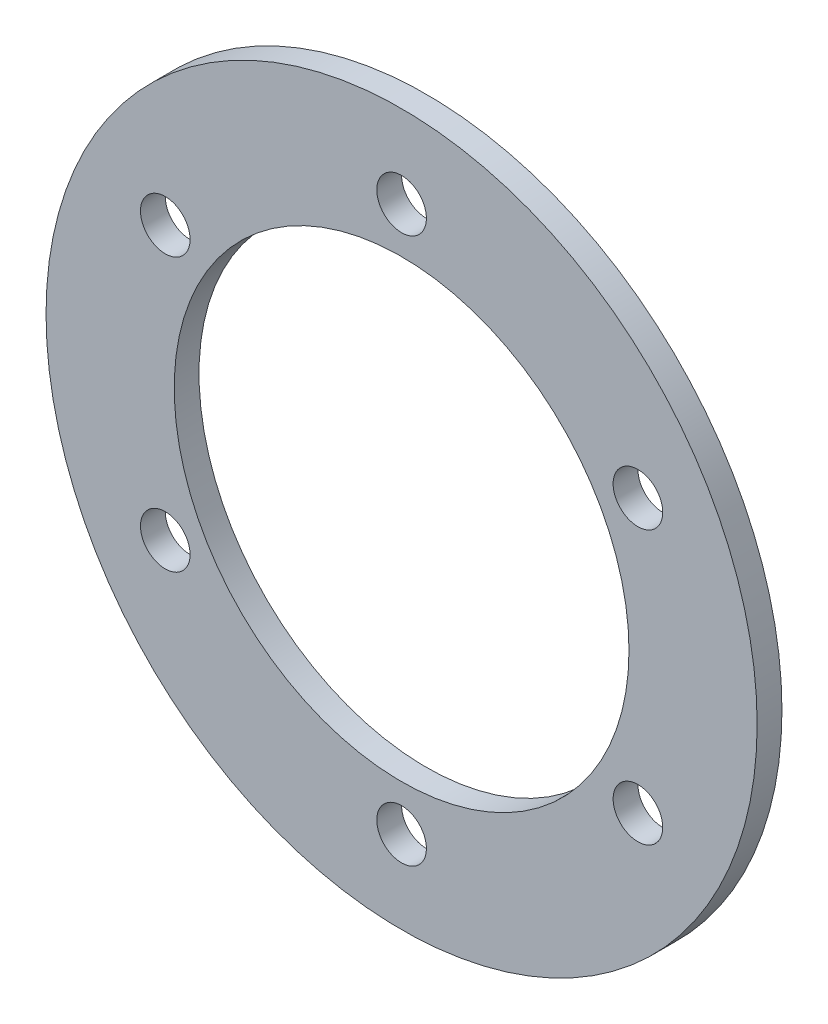
SolidWorks part; units mm, degrees
ref_plane "Front Plane" through (0, 0, 0) normal (0, 0, 1) x (1, 0, 0)
ref_plane "Top Plane" through (0, 0, 0) normal (0, 1, 0) x (1, 0, 0)
ref_plane "Right Plane" through (0, 0, 0) normal (1, 0, 0) x (0, 0, -1)
sketch "Sketch1" plane through (0, 0, 0) normal (0, 0, 1) x (1, 0, 0)
  circle A0 centre (0, 0) radius 43
  circle A1 centre (0, 0) radius 33 construction
  circle A3 centre (0, 33) radius 3
  circle A4 centre (0, 0) radius 27.5
  dimension "D1" = 86
  dimension "D2" = 6
  dimension "D3" = 66
  dimension "D4" = 55
extrude "Boss-Extrude2" add sketch "Sketch1" along normal blind 3 contours A0
extrude "Cut-Extrude1" cut sketch "Sketch1<3>" along normal through all contours A3
sketch "Sketch1<3>" plane through (0, 0, 0) normal (0, 0, 1) x (1, 0, 0) same geometry as "Sketch1"
pattern_circular "CirPattern2" count 6 over 360 about axis through (0, 0, 3) along (0, 0, -1) of "Cut-Extrude1" reverse direction yes
extrude "Cut-Extrude2" cut sketch "Sketch1<4>" along normal through all contours A4
sketch "Sketch1<4>" plane through (0, 0, 0) normal (0, 0, 1) x (1, 0, 0) same geometry as "Sketch1"
